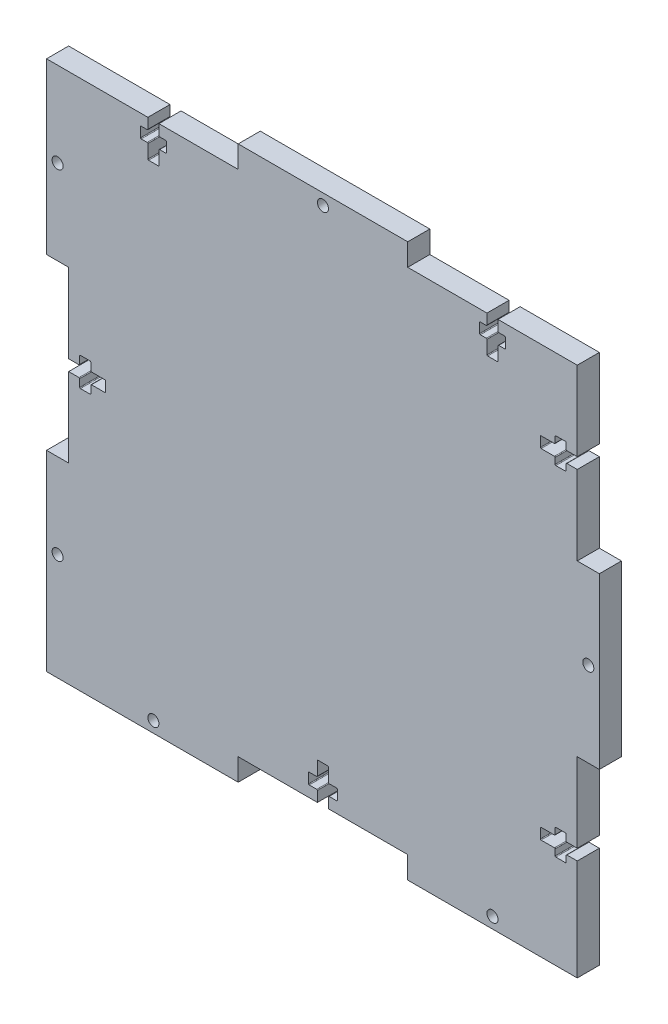
SolidWorks part; units mm, degrees
ref_plane "Front Plane" through (0, 0, 0) normal (0, 0, 1) x (1, 0, 0)
ref_plane "Top Plane" through (0, 0, 0) normal (0, 1, 0) x (1, 0, 0)
ref_plane "Right Plane" through (0, 0, 0) normal (1, 0, 0) x (0, 0, -1)
sketch "Sketch1" plane through (0, 0, 0) normal (0, 0, 1) x (1, 0, 0)
  line L0 (-69, 69) -> (-23, 69)
  line L5 (-75, -75) -> (75, -75) construction
  line L6 (-75, -75) -> (-75, 75) construction
  line L7 (-75, 75) -> (75, 75) construction
  line L8 (75, -75) -> (75, 75) construction
  line L9 (75, 23) -> (69, 23)
  line L10 (69, -23) -> (75, -23)
  line L11 (-69, -69) -> (69, -69) construction
  line L12 (-69, -69) -> (-69, 69) construction
  line L13 (-69, 69) -> (69, 69) construction
  line L14 (69, -69) -> (69, 69) construction
  line L15 (-69, -69) -> (69, 69) construction
  line L16 (69, -69) -> (69, -23)
  line L17 (-23, 69) -> (-23, 75)
  line L18 (-23, 75) -> (23, 75)
  line L19 (23, 75) -> (23, 69)
  line L20 (23, 69) -> (69, 69)
  line L21 (75, -23) -> (75, 23)
  line L22 (69, 23) -> (69, 69)
  line L23 (-75, 23) -> (-69, 23)
  line L24 (-69, 69) -> (-75, 69)
  line L25 (-75, 69) -> (-75, 23)
  line L26 (69, -69) -> (69, -75)
  line L27 (69, -75) -> (23, -75)
  line L28 (23, -75) -> (23, -69)
  line L29 (23, -69) -> (-23, -69)
  line L30 (-23, -69) -> (-23, -75)
  line L31 (-23, -75) -> (-69, -75)
  line L32 (-69, -75) -> (-69, -69)
  line L33 (-69, 23) -> (-69, -23)
  line L34 (-69, -23) -> (-75, -23)
  line L35 (-75, -23) -> (-75, -69)
  line L36 (-75, -69) -> (-69, -69)
  line L37 (-46, 69) -> (-46, -75) construction
  line L38 (-69, 69) -> (69, -69) construction
  point P0 (0, 0)
  point P6 (-7, -7)
  point P26 (0, -75)
  point P27 (-75, 0)
  dimension "D1" = 150
  dimension "D2" = 150
  dimension "D3" = 6
  dimension "D4" = 138
  dimension "D5" = 46
  dimension "D6" = 6
  dimension "D7" = 6
extrude "Box Side" add sketch "Sketch1" along normal blind 6
sketch "Sketch2" plane through (0, 0, 6) normal (0, 0, 1) x (1, 0, 0)
  line L0 (23, 72) -> (-23, 72) construction
  line L1 (23, 75) -> (23, 69) construction
  line L2 (-23, 69) -> (-23, 75) construction
  line L3 (-46, 69) -> (-46, -75) construction
  line L5 (0, 75) -> (0, 69) construction
  line L6 (-23, 75) -> (23, 75) construction
  line L7 (-69, 69) -> (69, 69) construction
  line L16 (-46, 69) -> (-46, -75) construction
  line L21 (0, -69) -> (0, 69) construction
  line L35 (-69, 69) -> (-23, 69) construction
  line L36 (-44.5, 69) -> (-44.5, 66.2)
  line L37 (-44.3, 66) -> (-42.7, 66)
  line L38 (-42.5, 65.8) -> (-42.5, 63.2)
  line L39 (-42.7, 63) -> (-44.3, 63)
  line L40 (-44.5, 62.8) -> (-44.5, 59.2)
  line L46 (-44.7, 59) -> (-47.3, 59)
  line L48 (-44.5, 69) -> (-47.5, 69)
  line L51 (-47.5, 62.8) -> (-47.5, 59.2)
  line L52 (-49.3, 63) -> (-47.7, 63)
  line L53 (-49.5, 65.8) -> (-49.5, 63.2)
  line L54 (-47.7, 66) -> (-49.3, 66)
  line L55 (-47.5, 69) -> (-47.5, 66.2)
  line L56 (47.5, 69) -> (47.5, 66.2)
  line L57 (47.7, 66) -> (49.3, 66)
  line L58 (49.5, 65.8) -> (49.5, 63.2)
  line L59 (49.3, 63) -> (47.7, 63)
  line L60 (47.5, 62.8) -> (47.5, 59.2)
  line L61 (44.5, 69) -> (47.5, 69)
  line L62 (44.7, 59) -> (47.3, 59)
  line L63 (44.5, 62.8) -> (44.5, 59.2)
  line L64 (42.7, 63) -> (44.3, 63)
  line L65 (42.5, 65.8) -> (42.5, 63.2)
  line L66 (44.3, 66) -> (42.7, 66)
  line L67 (44.5, 69) -> (44.5, 66.2)
  line L68 (-69, -69) -> (69, 69) construction
  line L69 (-69, -69) -> (69, 69) construction
  line L70 (75, 0) -> (69, 0) construction
  line L71 (72, 23) -> (72, -23) construction
  line L72 (69, 44.5) -> (66.2, 44.5)
  line L73 (66, 44.3) -> (66, 42.7)
  line L74 (65.8, 42.5) -> (63.2, 42.5)
  line L75 (63, 42.7) -> (63, 44.3)
  line L76 (62.8, 44.5) -> (59.2, 44.5)
  line L77 (59, 44.7) -> (59, 47.3)
  line L78 (69, 44.5) -> (69, 47.5)
  line L79 (62.8, 47.5) -> (59.2, 47.5)
  line L80 (63, 49.3) -> (63, 47.7)
  line L81 (65.8, 49.5) -> (63.2, 49.5)
  line L82 (66, 47.7) -> (66, 49.3)
  line L83 (69, 47.5) -> (66.2, 47.5)
  line L84 (69, -47.5) -> (66.2, -47.5)
  line L85 (66, -47.7) -> (66, -49.3)
  line L86 (65.8, -49.5) -> (63.2, -49.5)
  line L87 (63, -49.3) -> (63, -47.7)
  line L88 (62.8, -47.5) -> (59.2, -47.5)
  line L89 (69, -44.5) -> (69, -47.5)
  line L90 (59, -44.7) -> (59, -47.3)
  line L91 (62.8, -44.5) -> (59.2, -44.5)
  line L92 (63, -42.7) -> (63, -44.3)
  line L93 (65.8, -42.5) -> (63.2, -42.5)
  line L94 (66, -44.3) -> (66, -42.7)
  line L95 (69, -44.5) -> (66.2, -44.5)
  line L120 (-69, 69) -> (69, -69) construction
  line L121 (-69, 69) -> (69, -69) construction
  line L122 (-1.5, -69) -> (1.5, -69)
  line L123 (-23, -69) -> (23, -69) construction
  line L124 (1.5, -69) -> (1.5, -66.2)
  line L125 (1.7, -66) -> (3.7, -66)
  line L126 (3.9, -65.8) -> (3.9, -63.2)
  line L127 (3.7, -63) -> (1.7, -63)
  line L128 (1.5, -62.8) -> (1.5, -59.2)
  line L129 (1.3, -59) -> (-1.3, -59)
  line L130 (-1.5, -62.8) -> (-1.5, -59.2)
  line L131 (-3.7, -63) -> (-1.7, -63)
  line L132 (-3.9, -65.8) -> (-3.9, -63.2)
  line L133 (-1.7, -66) -> (-3.7, -66)
  line L134 (-1.5, -69) -> (-1.5, -66.2)
  line L135 (-69, -1.5) -> (-66.2, -1.5)
  line L136 (-66, -1.7) -> (-66, -3.7)
  line L137 (-65.8, -3.9) -> (-63.2, -3.9)
  line L138 (-63, -3.7) -> (-63, -1.7)
  line L139 (-62.8, -1.5) -> (-59.2, -1.5)
  line L140 (-59, 1.3) -> (-59, -1.3)
  line L141 (-62.8, 1.5) -> (-59.2, 1.5)
  line L142 (-63, 3.7) -> (-63, 1.7)
  line L143 (-65.8, 3.9) -> (-63.2, 3.9)
  line L144 (-66, 1.7) -> (-66, 3.7)
  line L145 (-69, 1.5) -> (-66.2, 1.5)
  line L146 (-69, -1.5) -> (-69, 1.5)
  line L147 (-69, -72) -> (-23, -72) construction
  line L148 (-69, -69) -> (-69, -75) construction
  line L149 (-23, -75) -> (-23, -69) construction
  circle A0 centre (0, 72) radius 1.5
  arc A1 (-44.5, 59.2) -> (-44.7, 59) centre (-44.7, 59.2) cw
  arc A2 (-44.3, 63) -> (-44.5, 62.8) centre (-44.3, 62.8) ccw
  arc A3 (-42.5, 63.2) -> (-42.7, 63) centre (-42.7, 63.2) cw
  arc A4 (-42.7, 66) -> (-42.5, 65.8) centre (-42.7, 65.8) cw
  arc A5 (-44.5, 66.2) -> (-44.3, 66) centre (-44.3, 66.2) ccw
  arc A6 (-47.5, 66.2) -> (-47.7, 66) centre (-47.7, 66.2) cw
  arc A7 (-49.3, 66) -> (-49.5, 65.8) centre (-49.3, 65.8) ccw
  arc A8 (-49.5, 63.2) -> (-49.3, 63) centre (-49.3, 63.2) ccw
  arc A9 (-47.7, 63) -> (-47.5, 62.8) centre (-47.7, 62.8) cw
  arc A10 (-47.5, 59.2) -> (-47.3, 59) centre (-47.3, 59.2) ccw
  arc A11 (47.5, 59.2) -> (47.3, 59) centre (47.3, 59.2) cw
  arc A12 (47.7, 63) -> (47.5, 62.8) centre (47.7, 62.8) ccw
  arc A13 (49.5, 63.2) -> (49.3, 63) centre (49.3, 63.2) cw
  arc A14 (49.3, 66) -> (49.5, 65.8) centre (49.3, 65.8) cw
  arc A15 (47.5, 66.2) -> (47.7, 66) centre (47.7, 66.2) ccw
  arc A16 (44.5, 66.2) -> (44.3, 66) centre (44.3, 66.2) cw
  arc A17 (42.7, 66) -> (42.5, 65.8) centre (42.7, 65.8) ccw
  arc A18 (42.5, 63.2) -> (42.7, 63) centre (42.7, 63.2) ccw
  arc A19 (44.3, 63) -> (44.5, 62.8) centre (44.3, 62.8) cw
  arc A20 (44.5, 59.2) -> (44.7, 59) centre (44.7, 59.2) ccw
  arc A21 (59.2, 44.5) -> (59, 44.7) centre (59.2, 44.7) cw
  arc A22 (63, 44.3) -> (62.8, 44.5) centre (62.8, 44.3) ccw
  arc A23 (63.2, 42.5) -> (63, 42.7) centre (63.2, 42.7) cw
  arc A24 (66, 42.7) -> (65.8, 42.5) centre (65.8, 42.7) cw
  arc A25 (66.2, 44.5) -> (66, 44.3) centre (66.2, 44.3) ccw
  arc A26 (66.2, 47.5) -> (66, 47.7) centre (66.2, 47.7) cw
  arc A27 (66, 49.3) -> (65.8, 49.5) centre (65.8, 49.3) ccw
  arc A28 (63.2, 49.5) -> (63, 49.3) centre (63.2, 49.3) ccw
  arc A29 (63, 47.7) -> (62.8, 47.5) centre (62.8, 47.7) cw
  arc A30 (59.2, 47.5) -> (59, 47.3) centre (59.2, 47.3) ccw
  arc A31 (59.2, -47.5) -> (59, -47.3) centre (59.2, -47.3) cw
  arc A32 (63, -47.7) -> (62.8, -47.5) centre (62.8, -47.7) ccw
  arc A33 (63.2, -49.5) -> (63, -49.3) centre (63.2, -49.3) cw
  arc A34 (66, -49.3) -> (65.8, -49.5) centre (65.8, -49.3) cw
  arc A35 (66.2, -47.5) -> (66, -47.7) centre (66.2, -47.7) ccw
  arc A36 (66.2, -44.5) -> (66, -44.3) centre (66.2, -44.3) cw
  arc A37 (66, -42.7) -> (65.8, -42.5) centre (65.8, -42.7) ccw
  arc A38 (63.2, -42.5) -> (63, -42.7) centre (63.2, -42.7) ccw
  arc A39 (63, -44.3) -> (62.8, -44.5) centre (62.8, -44.3) cw
  arc A40 (59.2, -44.5) -> (59, -44.7) centre (59.2, -44.7) ccw
  circle A41 centre (72, 0) radius 1.5
  arc A62 (1.5, -59.2) -> (1.3, -59) centre (1.3, -59.2) ccw
  arc A63 (1.7, -63) -> (1.5, -62.8) centre (1.7, -62.8) cw
  arc A64 (3.9, -63.2) -> (3.7, -63) centre (3.7, -63.2) ccw
  arc A65 (3.7, -66) -> (3.9, -65.8) centre (3.7, -65.8) ccw
  arc A66 (1.5, -66.2) -> (1.7, -66) centre (1.7, -66.2) cw
  arc A67 (-1.5, -66.2) -> (-1.7, -66) centre (-1.7, -66.2) ccw
  arc A68 (-3.7, -66) -> (-3.9, -65.8) centre (-3.7, -65.8) cw
  arc A69 (-3.9, -63.2) -> (-3.7, -63) centre (-3.7, -63.2) cw
  arc A70 (-1.7, -63) -> (-1.5, -62.8) centre (-1.7, -62.8) ccw
  arc A71 (-1.5, -59.2) -> (-1.3, -59) centre (-1.3, -59.2) cw
  arc A72 (-59.2, -1.5) -> (-59, -1.3) centre (-59.2, -1.3) ccw
  arc A73 (-63, -1.7) -> (-62.8, -1.5) centre (-62.8, -1.7) cw
  arc A74 (-63.2, -3.9) -> (-63, -3.7) centre (-63.2, -3.7) ccw
  arc A75 (-66, -3.7) -> (-65.8, -3.9) centre (-65.8, -3.7) ccw
  arc A76 (-66.2, -1.5) -> (-66, -1.7) centre (-66.2, -1.7) cw
  arc A77 (-66.2, 1.5) -> (-66, 1.7) centre (-66.2, 1.7) ccw
  arc A78 (-66, 3.7) -> (-65.8, 3.9) centre (-65.8, 3.7) cw
  arc A79 (-63.2, 3.9) -> (-63, 3.7) centre (-63.2, 3.7) cw
  arc A80 (-63, 1.7) -> (-62.8, 1.5) centre (-62.8, 1.7) ccw
  arc A81 (-59.2, 1.5) -> (-59, 1.3) centre (-59.2, 1.3) cw
  circle A82 centre (-46, -72) radius 1.5
  circle A83 centre (46, -72) radius 1.5
  circle A84 centre (-72, 46) radius 1.5
  circle A85 centre (-72, -46) radius 1.5
  point P6 (0, 72)
  point P38 (0, 0)
  point P56 (-46, 59)
  point P88 (46, 59)
  point P161 (59, 46)
  point P162 (59, -46)
  point P198 (0, -59)
  point P231 (-59, 0)
  dimension "D1" = 3
  dimension "D2" = 0.2
  dimension "D8" = 0.2
  dimension "D14" = 3
  dimension "D3" = 3
  dimension "D4" = 3
  dimension "D5" = 4
  dimension "D6" = 2
  dimension "D7" = 1.5
  dimension "D9" = 3
  dimension "D10" = 3
  dimension "D11" = 4
  dimension "D12" = 1.5
  dimension "D13" = 2
extrude "Screw Cut-outs" cut sketch "Sketch2" against normal through all
sketch "Sketch3" plane through (0, 0, 6) normal (0, 0, 1) x (1, 0, 0)
  line L1 (-75, -69) -> (-69, -69)
  line L2 (-75, -69) -> (-75, -75)
  line L3 (-75, -75) -> (-69, -75)
  line L4 (-69, -69) -> (-69, -75)
  line L5 (69, -75) -> (75, -75)
  line L6 (69, -75) -> (69, -69)
  line L7 (69, -69) -> (75, -69)
  line L8 (75, -75) -> (75, -69)
  line L10 (69, -75) -> (69, -47.5) construction
  line L13 (-69, -69) -> (69, -69) construction
extrude "Boss-Extrude2" add sketch "Sketch3" against normal blind 6 contours L2 L3 L4 L1
